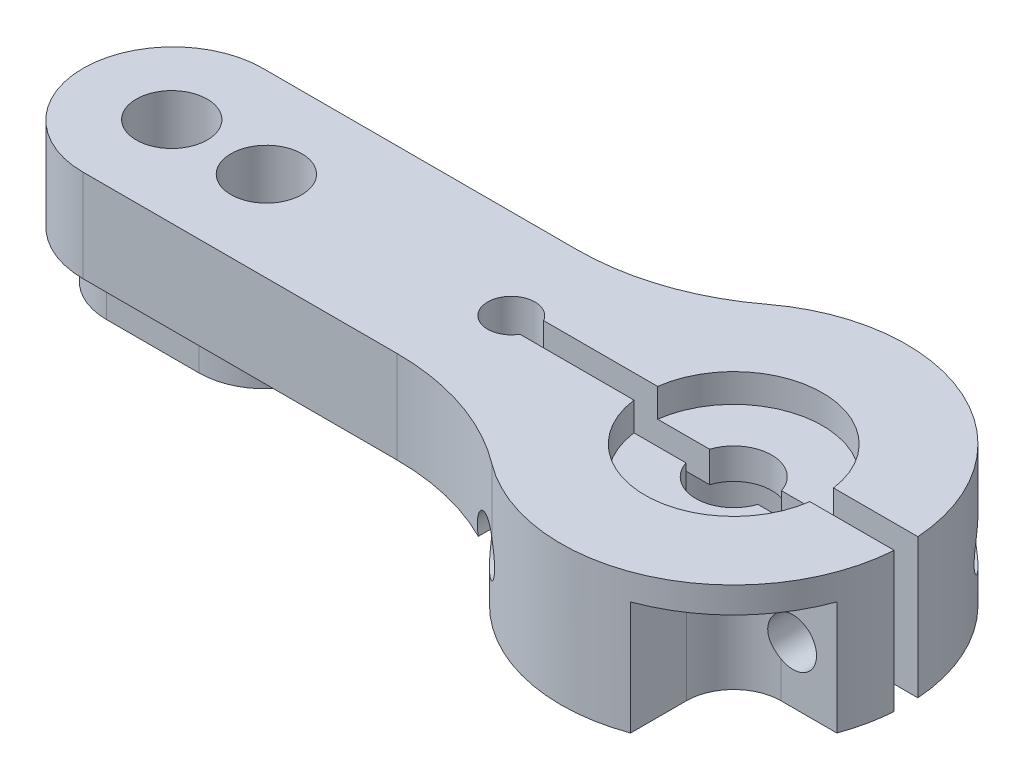
SolidWorks part; units mm, degrees
ref_plane "Plan de face" through (0, 0, 0) normal (0, 0, 1) x (1, 0, 0)
ref_plane "Plan de dessus" through (0, 0, 0) normal (0, 1, 0) x (1, 0, 0)
ref_plane "Plan de droite" through (0, 0, 0) normal (1, 0, 0) x (0, 0, -1)
sketch "Esquisse1" plane through (0, 0, 0) normal (0, 1, 0) x (1, 0, 0)
  line L0 (0, 0) -> (-23.7, 0) construction
  line L1 (-10.4331, 3.8) -> (-23.7, 3.8)
  line L4 (-10.4331, -3.8) -> (-23.7, -3.8)
  line L5 (0, -7.3) -> (0, 7.3) construction
  arc A3 (-4.4024, 5.8231) -> (-4.4024, -5.8231) centre (0, 0) cw
  arc A4 (-4.4024, 5.8231) -> (-10.4331, 3.8) centre (-10.4331, 13.8) cw
  arc A5 (-23.7, 3.8) -> (-23.7, -3.8) centre (-23.7, 0) ccw
  arc A6 (-4.4024, -5.8231) -> (-10.4331, -3.8) centre (-10.4331, -13.8) ccw
  point P13 (-27.5, 0)
  point P14 (7.3, 0)
  point P16 (0, 0)
  dimension "D1" = 14.6
  dimension "D2" = 10
  dimension "D3" = 34.8
  dimension "D5" = 7.6
extrude "Boss.-Extru.1" add sketch "Esquisse1" along normal blind 3.9
sketch "Esquisse2" plane through (0, 0, 0) normal (0, -1, 0) x (-1, 0, 0)
  line L0 (0, 0) -> (27.5, 0) construction
  line L1 (23.7, 0) -> (19.8, 0) construction
  line L2 (23.7, -2.8) -> (19.8, -2.8)
  line L3 (23.7, 2.8) -> (19.8, 2.8)
  circle A0 centre (0, 0) radius 7.3
  arc A1 (4.4024, 5.8231) -> (4.4024, -5.8231) centre (0, 0) ccw construction
  arc A3 (23.7, -3.8) -> (23.7, 3.8) centre (23.7, 0) ccw construction
  arc A4 (23.7, -2.8) -> (23.7, 2.8) centre (23.7, 0) ccw
  arc A5 (19.8, 2.8) -> (19.8, -2.8) centre (19.8, 0) ccw
  point P13 (21.75, 0)
  point P18 (26.5, 0)
  point P19 (17, 0)
  dimension "D3" = 5.6
  dimension "D2" = 9.5
extrude "Boss.-Extru.2" add sketch "Esquisse2" along normal blind 2
hole_wizard "Dégagement M31" positions "Esquisse7" profile "Esquisse8" hole size "M3" standard "DIN" end condition through all
sketch "Esquisse7" plane through (0, 3.9, 0) normal (0, 1, 0) x (1, 0, 0)
  point P0 (0, 0)
sketch "Esquisse8" plane through (0, 3.9, 0) normal (1, 0, 0) x (0, 0, 1)
  line L0 (0, 0) -> (0, 5.9)
  line L1 (0, 5.9) -> (1.6, 5.9)
  line L2 (1.6, 5.9) -> (1.6, 0)
  line L5 (1.6, 0) -> (0, 0)
  line L11 (0, -6.35) -> (0, 107.95) construction
  dimension "Diamètre du perçage jusqu'au prochain" = 3.2
  dimension "Profondeur du perçage jusqu'au prochain" = 5.9
ref_axis "Axe1" through (0, -2, 0) along (0, 1, 0)
hole_wizard "Diamètre du perçage Ø3.0 (3)1" positions "Esquisse4" profile "Esquisse5" hole size "Ø3.0" standard "DIN" end condition through all
sketch "Esquisse4" plane through (0, -2, 0) normal (0, -1, 0) x (-1, 0, 0)
  line L0 (17, 0) -> (26.5, 0) construction
  line L2 (21.75, -2.8) -> (21.75, 2.8) construction
  line L3 (19.8, -2.8) -> (23.7, -2.8) construction
  line L4 (23.7, 2.8) -> (19.8, 2.8) construction
  arc A0 (19.8, 2.8) -> (19.8, -2.8) centre (19.8, 0) ccw construction
  arc A1 (23.7, -2.8) -> (23.7, 2.8) centre (23.7, 0) ccw construction
  point P0 (19.75, 0)
  point P25 (23.75, 0)
  dimension "D1" = 4
sketch "Esquisse5" plane through (-19.75, -2, 0) normal (1, 0, 0) x (0, 0, -1)
  line L0 (0, 0) -> (0, 5.9)
  line L1 (0, 5.9) -> (1.5, 5.9)
  line L2 (1.5, 5.9) -> (1.5, 0)
  line L5 (1.5, 0) -> (0, 0)
  line L11 (0, -6.35) -> (0, 107.95) construction
  dimension "Diamètre du perçage jusqu'au prochain" = 3
  dimension "Profondeur du perçage jusqu'au prochain" = 5.9
sketch "Esquisse6" plane through (0, -2, 0) normal (0, -1, 0) x (1, 0, 0)
  circle A0 centre (0, 0) radius 2.75
  dimension "D1" = 5.5
extrude "Enlèv. mat.-Extru.1" cut sketch "Esquisse6" against normal blind 3.4
sketch "Esquisse9" plane through (0, 3.9, 0) normal (0, 1, 0) x (1, 0, 0)
  circle A0 centre (0, 0) radius 3.75
  dimension "D1" = 7.5
extrude "Enlèv. mat.-Extru.2" cut sketch "Esquisse9" against normal blind 1.2
sketch "Esquisse10" plane through (0, 3.9, 0) normal (0, 1, 0) x (1, 0, 0)
  line L0 (-8.534, 0.5) -> (7.9871, 0.5)
  line L1 (0, 0) -> (5.8746, 0) construction
  line L2 (-8.534, -0.5) -> (7.9871, -0.5)
  line L3 (7.9871, -0.5) -> (7.9871, 0.5)
  arc A0 (-8.534, 0.5) -> (-8.534, -0.5) centre (-9.4, 0) ccw
  arc A1 (-4.4024, -5.8231) -> (-4.4024, 5.8231) centre (0, 0) ccw construction
  point P5 (7.3, 0)
  dimension "D2" = 2
  dimension "D1" = 16.7
  dimension "D3" = 1
extrude "Enlèv. mat.-Extru.3" cut sketch "Esquisse10" against normal through all
sketch "Esquisse11" plane through (0, -2, 0) normal (0, -1, 0) x (1, 0, 0)
  line L0 (2.5, 6.8586) -> (2.5, 4.5)
  line L2 (4.5, 2.5) -> (6.8586, 2.5)
  line L3 (0, 0) -> (3.5106, -3.5106) construction
  line L4 (-2.5, -4.5) -> (-2.5, -6.8586)
  line L5 (-6.8586, -2.5) -> (-4.5, -2.5)
  line L6 (0, 0) -> (3.8671, 0) construction
  line L7 (2.7042, 0.5) -> (7.2829, 0.5) construction
  line L8 (-9.0984, -3.8895) -> (-4.5, -6.8586)
  line L9 (-4.5, -6.8586) -> (-2.5, -6.8586)
  arc A0 (7.2829, 0.5) -> (-7.2829, 0.5) centre (0, 0) ccw construction
  arc A1 (2.5, 4.5) -> (4.5, 2.5) centre (4.5, 4.5) ccw
  arc A2 (6.8586, 2.5) -> (2.5, 6.8586) centre (0, 0) ccw
  arc A3 (-4.5, -2.5) -> (-2.5, -4.5) centre (-4.5, -4.5) cw
  arc A5 (-6.8586, -2.5) -> (-9.0984, -3.8895) centre (-6.8586, -5) ccw
  arc A6 (-4.4024, -5.8231) -> (-10.4331, -3.8) centre (-10.4331, -13.8) ccw construction
  dimension "D4" = 2
  dimension "D5" = 2.5
  dimension "D1" = 2.5
  dimension "D2" = 45
  dimension "D3" = 2
extrude "Enlèv. mat.-Extru.4" cut sketch "Esquisse11" against normal blind 4.8
sketch "Esquisse14" plane through (0, 0, 0) normal (0, 0, 1) x (1, 0, 0)
  line L0 (0, 0) -> (0, 1.3072) construction
  line L1 (4.5, 2.8) -> (4.5, -2) construction
  circle A0 centre (5, 0.4) radius 1
  circle A1 centre (-5, 0.4) radius 1
  point P10 (4.5, 0.4)
  dimension "D1" = 2
  dimension "D2" = 10
extrude "Enlèv. mat.-Extru.5" cut sketch "Esquisse14" against normal through all and the other way through all
